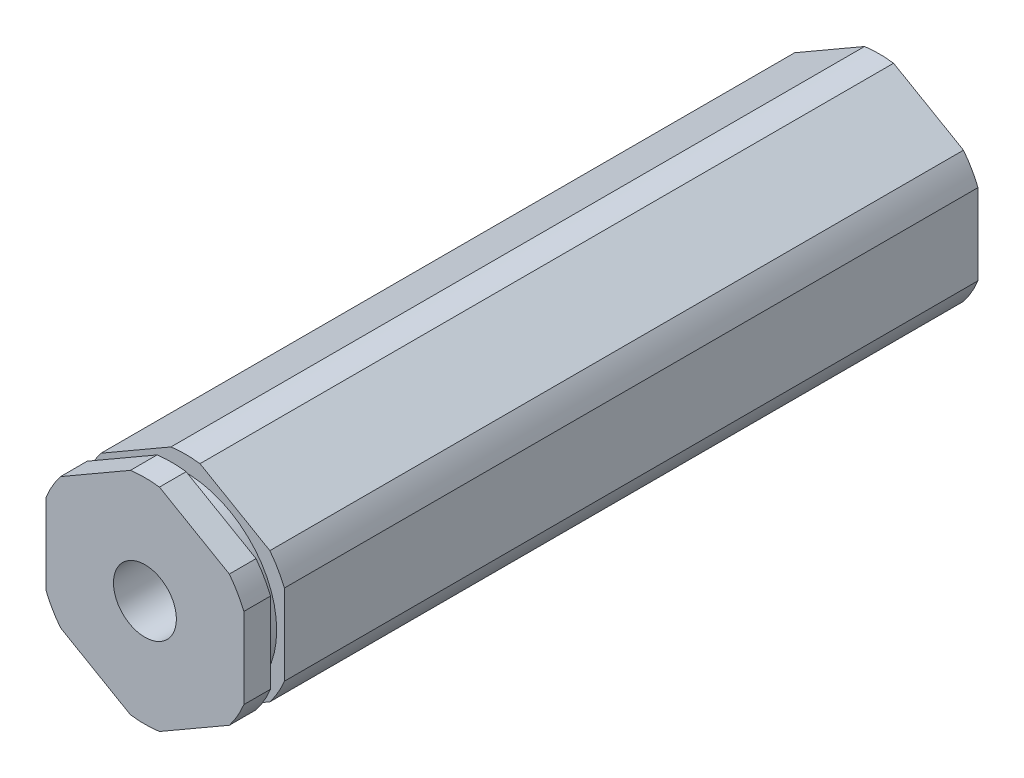
SolidWorks part; units mm, degrees
ref_plane "Front Plane" through (0, 0, 0) normal (0, 0, 1) x (1, 0, 0)
ref_plane "Top Plane" through (0, 0, 0) normal (0, 1, 0) x (1, 0, 0)
ref_plane "Right Plane" through (0, 0, 0) normal (1, 0, 0) x (0, 0, -1)
sketch "Sketch1" plane through (0, 0, 0) normal (0, 0, 1) x (1, 0, 0)
  line L1 (0, 7.3323) -> (-6.35, 3.6662)
  line L2 (-6.35, 3.6662) -> (-6.35, -3.6662)
  line L3 (-6.35, -3.6662) -> (0, -7.3323)
  line L4 (0, -7.3323) -> (6.35, -3.6662)
  line L5 (6.35, -3.6662) -> (6.35, 3.6662)
  line L6 (6.35, 3.6662) -> (0, 7.3323)
  circle A0 centre (0, 0) radius 6.35 construction
  circle A1 centre (0, 0) radius 6.858
  dimension "D1" = 12.7
  dimension "D2" = 13.716
extrude "Boss-Extrude1" add sketch "Sketch1" along normal mid plane 47.1297 contours L5 A1 L6 L1 L2 L3 L4 region at (0, 0, 0)
sketch "Sketch6" plane through (0, 0, 0) normal (0, 0, 1) x (1, 0, 0)
  line L0 (5.4183, 4.2041) -> (0.9317, 6.7944) construction
  circle A0 centre (0, 0) radius 6.35
hole_wizard "#10-32 Tapped Hole1" positions "3DSketch1" profile "Sketch2" tap size "#10-32" standard "ANSI Inch"
sketch3d "3DSketch1"
  line L0 (0, 0, 23.5648) -> (0, 0, -23.5648) construction
  line L1 (0, 0, 23.5648) -> (0, 0, -23.5648) construction
  point P0 (0, 0, 23.5648)
  point P4 (0, 0, -23.5648)
sketch "Sketch2" plane through (0, 0, 23.5648) normal (1, 0, 0) x (0, -1, 0)
  line L0 (0, 0) -> (0, 17.5608)
  line L1 (0, 17.5608) -> (2.0193, 16.3474)
  line L2 (2.0193, 16.3474) -> (2.0193, 0)
  line L5 (2.0193, 0) -> (0, 0)
  line L10 (0, 17.5608) -> (-2.0193, 16.3474) construction
  line L11 (0, -6.35) -> (0, 107.95) construction
  dimension "Tap Drill Dia." = 4.0386
  dimension "Tap Drill Depth" = 16.3474
  dimension "Drill Angle" = 118
cosmetic thread "Hole Thread1" parameters "D1"=13.97, "D2"=4.826
cosmetic thread "Hole Thread2" parameters "D1"=13.97, "D2"=4.826
sketch "Sketch5" plane through (0, 0, 0) normal (1, 0, 0) x (0, 0, -1)
  line L0 (23.5648, 6.858) -> (-23.5648, 6.858) construction
  line L1 (-21.8503, 6.858) -> (-20.9613, 6.858)
  line L2 (-21.8503, 6.858) -> (-21.8503, 5.8547)
  line L3 (-21.8503, 5.8547) -> (-20.9613, 5.8547)
  line L4 (-20.9613, 6.858) -> (-20.9613, 5.8547)
  line L5 (-165.0472, 0) -> (-158.8423, 0) construction
  dimension "D1" = 5.8547
  dimension "D2" = 0.889
  dimension "D3" = 1.7145
revolve "Cut-Revolve1" cut sketch "Sketch5" angle 360 about L5
